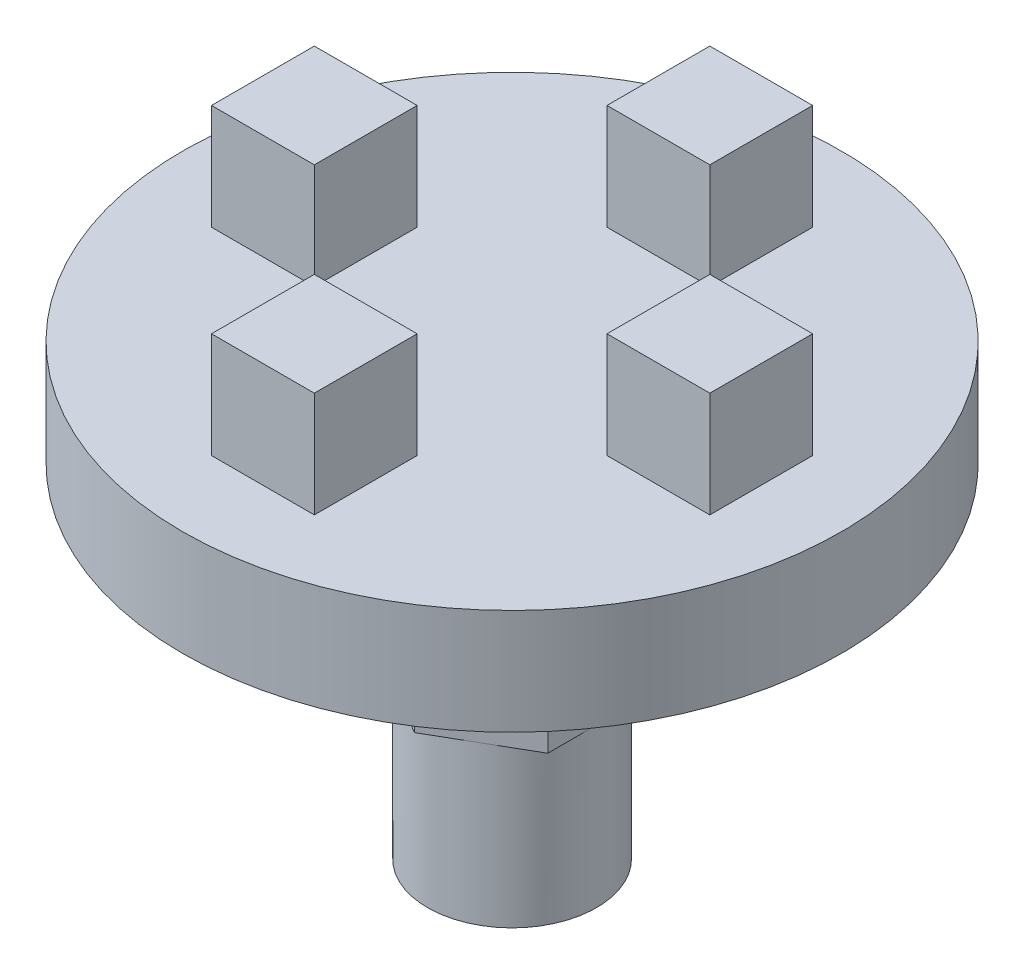
SolidWorks part; units mm, degrees
ref_plane "Front Plane" through (0, 0, 0) normal (0, 0, 1) x (1, 0, 0)
ref_plane "Top Plane" through (0, 0, 0) normal (0, 1, 0) x (1, 0, 0)
ref_plane "Right Plane" through (0, 0, 0) normal (1, 0, 0) x (0, 0, -1)
sketch "Sketch1" plane through (0, 0, 0) normal (0, 1, 0) x (1, 0, 0)
  circle A0 centre (0, 0) radius 12.5
  dimension "D1" = 25
extrude "Boss-Extrude1" add sketch "Sketch1" along normal mid plane 4
sketch "Sketch2" plane through (0, 2, 0) normal (0, 1, 0) x (1, 0, 0)
  line L1 (-2, 9.5) -> (2, 9.5) construction
  line L2 (-2, 9.5) -> (-2, 5.5) construction
  line L3 (-2, 5.5) -> (2, 5.5) construction
  line L4 (2, 9.5) -> (2, 5.5) construction
  line L5 (-1.95, 9.45) -> (-1.95, 5.55)
  line L6 (-1.95, 5.55) -> (1.95, 5.55)
  line L7 (1.95, 9.45) -> (1.95, 5.55)
  line L8 (-1.95, 9.45) -> (1.95, 9.45)
  line L9 (9.45, 1.95) -> (5.55, 1.95)
  line L10 (5.55, 1.95) -> (5.55, -1.95)
  line L11 (9.45, -1.95) -> (5.55, -1.95)
  line L12 (9.45, 1.95) -> (9.45, -1.95)
  line L13 (1.95, -9.45) -> (1.95, -5.55)
  line L14 (1.95, -5.55) -> (-1.95, -5.55)
  line L15 (-1.95, -9.45) -> (-1.95, -5.55)
  line L16 (1.95, -9.45) -> (-1.95, -9.45)
  line L17 (-9.45, -1.95) -> (-5.55, -1.95)
  line L18 (-5.55, -1.95) -> (-5.55, 1.95)
  line L19 (-9.45, 1.95) -> (-5.55, 1.95)
  line L20 (-9.45, -1.95) -> (-9.45, 1.95)
  point P4 (0, 5.5)
  point P25 (0, 0)
  dimension "D1" = 5.5
  dimension "D2" = 4
  dimension "D3" = 4
  dimension "D4" = 0.05
  dimension "D5" = 4
extrude "Boss-Extrude3" add sketch "Sketch2" along normal blind 4
sketch "Sketch3" plane through (0, -2, 0) normal (0, -1, 0) x (1, 0, 0)
  circle A0 centre (0, 0) radius 5
  dimension "D1" = 10
extrude "Boss-Extrude4" add sketch "Sketch3" along normal blind 1
sketch "Sketch4" plane through (0, -3, 0) normal (0, -1, 0) x (1, 0, 0)
  line L1 (0, -3.7) -> (3.2043, -1.85)
  line L2 (3.2043, -1.85) -> (3.2043, 1.85)
  line L3 (3.2043, 1.85) -> (0, 3.7)
  line L4 (0, 3.7) -> (-3.2043, 1.85)
  line L5 (-3.2043, 1.85) -> (-3.2043, -1.85)
  line L6 (-3.2043, -1.85) -> (0, -3.7)
  circle A0 centre (0, 0) radius 3.7 construction
  circle A1 centre (0, 0) radius 3.2043 construction
  dimension "D1" = 7.4
extrude "Boss-Extrude5" add sketch "Sketch4" along normal blind 6
sketch "Sketch5" plane through (0, -9, 0) normal (0, -1, 0) x (-1, 0, 0)
  line L0 (0, 3.7) -> (-3.2043, 1.85) construction
  circle A0 centre (0, 0) radius 3.2043
extrude "Boss-Extrude6" add sketch "Sketch5" along normal blind 6
